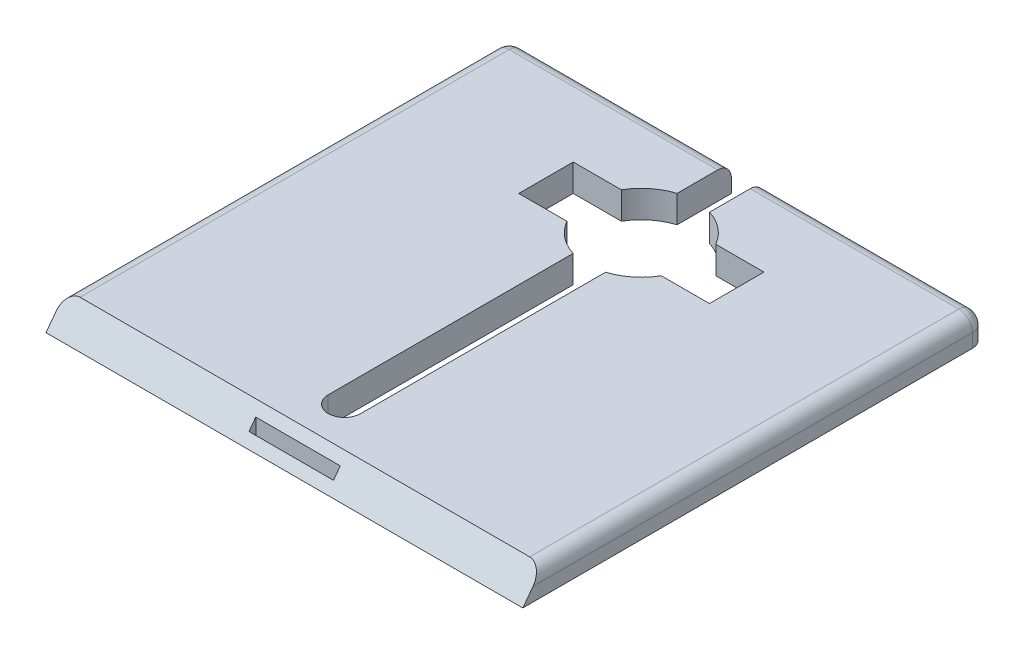
SolidWorks part; units mm, degrees
ref_plane "Ebene vorne" through (0, 0, 0) normal (0, 0, 1) x (1, 0, 0)
ref_plane "Ebene oben" through (0, 0, 0) normal (0, 1, 0) x (1, 0, 0)
ref_plane "Ebene rechts" through (0, 0, 0) normal (1, 0, 0) x (0, 0, -1)
sketch "Skizze1" plane through (0, 0, 0) normal (0, 1, 0) x (1, 0, 0)
  line L1 (-8.75, -8.5) -> (8.75, -8.5)
  line L2 (-8.75, -8.5) -> (-8.75, 8.5)
  line L3 (-8.75, 8.5) -> (8.75, 8.5)
  line L4 (8.75, -8.5) -> (8.75, 8.5)
  line L5 (-8.75, -8.5) -> (8.75, 8.5) construction
  line L6 (-8.75, 8.5) -> (8.75, -8.5) construction
  point P0 (0, 0)
  dimension "D1" = 17
  dimension "D2" = 17.5
extrude "Aufsatz-Linear austragen1" add sketch "Skizze1" along normal blind 1
fillet "Verrundung1" radius 0.5 3 edges at (8.75, 1, 0) (0, 1, -8.5) (-8.75, 1, 0)
sketch "Skizze2" plane through (-8.75, 0, 0) normal (-1, 0, 0) x (0, 0, 1)
  line L0 (8.5, 0) -> (7.75, 1)
  line L1 (-8, 1) -> (8.5, 1) construction
  line L2 (7.75, 1) -> (8.5, 1)
  line L3 (8.5, 1) -> (8.5, 0)
  dimension "D1" = 0.75
extrude "Schnitt-Linear austragen1" cut sketch "Skizze2" against normal up to surface (17.5 mm away) up to face at (8.75, 0.25, 0)
fillet "Verrundung2" radius 0.5 4 edges at (8.6036, 0.8536, -8.3536) (-8.6036, 0.8536, -8.3536) (8.75, 0.25, -8.5) (-8.75, 0.25, -8.5)
sketch "Skizze5" plane through (0, 1, 0) normal (0, 1, 0) x (1, 0, 0)
  line L0 (-8.75, 8) -> (-8.75, -8.5) construction
  line L1 (-3.5, 3.6) -> (3.5, 3.6)
  line L2 (-3.5, 3.6) -> (-3.5, 5.6)
  line L3 (-3.5, 5.6) -> (3.5, 5.6)
  line L4 (3.5, 3.6) -> (3.5, 5.6)
  line L5 (-3.5, 3.6) -> (3.5, 5.6) construction
  line L6 (-3.5, 5.6) -> (3.5, 3.6) construction
  line L7 (-8.25, 8.5) -> (8.25, 8.5) construction
  circle A0 centre (0, 4.6) radius 2
  dimension "D2" = 4
  dimension "D1" = 7
  dimension "D3" = 2
  dimension "D4" = 8.75
  dimension "D5" = 3.9
extrude "Schlüsselloch" cut sketch "Skizze5" against normal up to surface (1 mm away) contours A0 L3 L2 L1 | L3 A0 | L1 A0 L3 | L1 A0 | A0 L1 L4 L3 region at (-2.7046, 1, -4.6) region at (0, 1, -4.6) region at (0, 1, -3.19) region at (2.7046, 1, -4.6) region at (0, 1, -6.01) up to face at (0, 0, -2.7012)
sketch "Skizze6" plane through (0, 1, 0) normal (0, 1, 0) x (1, 0, 0)
  line L0 (8.25, -7.75) -> (-8.25, -7.75) construction
  line L1 (-1.5515, -8.25) -> (1.5515, -8.25)
  line L2 (-1.5515, -8.25) -> (-1.5515, -8)
  line L3 (-1.5515, -8) -> (1.5515, -8)
  line L4 (1.5515, -8.25) -> (1.5515, -8)
  line L5 (-1.5515, -8.25) -> (1.5515, -8) construction
  line L6 (-1.5515, -8) -> (1.5515, -8.25) construction
  line L7 (-8.75, -8.125) -> (-8.75, -8.5) construction
  point P0 (0, -8.125)
  dimension "D1" = 0.25
  dimension "D2" = 0.25
  dimension "D3" = 8.75
extrude "Griff" cut sketch "Skizze6" against normal up to surface (1 mm away) up to face at (0, 0, -4.6)
sketch "Skizze7" plane through (0, 1, 0) normal (0, 1, 0) x (1, 0, 0)
  line L5 (0, 8.5) -> (0, -6.2955) construction
  line L6 (-8.25, 8.5) -> (8.25, 8.5) construction
  line L7 (0.5967, 8.5) -> (0.5967, -6.2955)
  line L8 (-0.5967, 8.5) -> (-0.5967, -6.2955)
  arc A0 (0.5967, 8.5) -> (-0.5967, 8.5) centre (0, 8.5) ccw
  arc A1 (-0.5967, -6.2955) -> (0.5967, -6.2955) centre (0, -6.2955) ccw
  point P4 (0, 1.1022)
extrude "Langloch_Antenne" cut sketch "Skizze7" against normal up to surface (1 mm away) up to face at (0, 0, 8.125)
